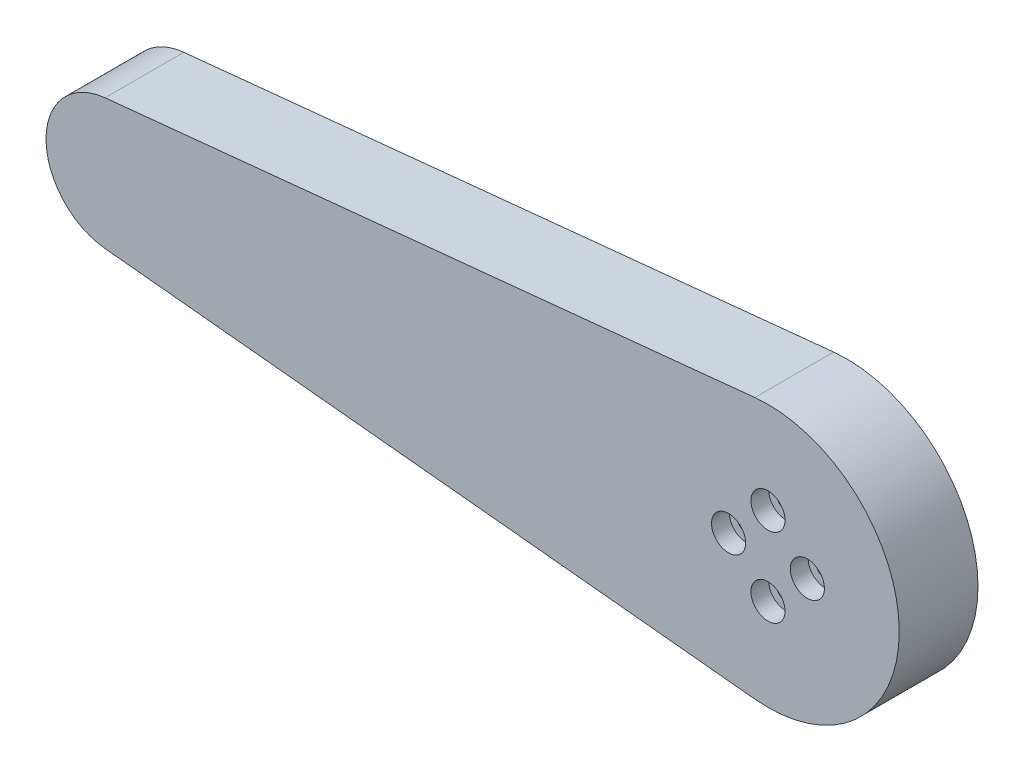
SolidWorks part; units mm, degrees
ref_plane "Front Plane" through (0, 0, 0) normal (0, 0, 1) x (1, 0, 0)
ref_plane "Top Plane" through (0, 0, 0) normal (0, 1, 0) x (1, 0, 0)
ref_plane "Right Plane" through (0, 0, 0) normal (1, 0, 0) x (0, 0, -1)
sketch "Sketch1" plane through (0, 0, 0) normal (0, 0, 1) x (1, 0, 0)
  line L0 (-126.25, 12.4373) -> (-2.5, 24.8747)
  line L1 (-126.25, -12.4373) -> (-2.5, -24.8747)
  circle A0 centre (0, 0) radius 12.5
  arc A1 (-2.5, -24.8747) -> (-2.5, 24.8747) centre (0, 0) ccw
  arc A2 (-126.25, 12.4373) -> (-126.25, -12.4373) centre (-125, 0) ccw
  dimension "D1" = 25
  dimension "D2" = 50
  dimension "D3" = 25
  dimension "D4" = 125
extrude "Boss-Extrude1" add sketch "Sketch1" along normal blind 15 contours L1 A1 L0 A2
hole_wizard "CBORE for M3 Hex Socket Head Cap Screw1" positions "Sketch3" profile "Sketch5" counterbore size "M3" standard "ISO" end condition up to next
sketch "Sketch3" plane through (0, 0, 15) normal (0, 0, 1) x (1, 0, 0)
  circle A0 centre (0, 0) radius 7.5
  point P0 (0, 7.5)
  point P13 (7.5, 0)
  point P15 (0, -7.5)
  point P17 (-7.5, 0)
  dimension "D1" = 15
sketch "Sketch5" plane through (0, 7.5, 15) normal (1, 0, 0) x (0, -1, 0)
  line L0 (0, 0) -> (0, 15)
  line L1 (0, 15) -> (1.7, 15)
  line L3 (1.7, 15) -> (1.7, 3.4)
  line L4 (1.7, 3.4) -> (3.25, 3.4)
  line L5 (3.25, 3.4) -> (3.25, 0)
  line L7 (3.25, 0) -> (0, 0)
  line L11 (0, -6.35) -> (0, 107.95) construction
  dimension "Thru Hole Dia." = 3.4
  dimension "Thru Hole Depth" = 15
  dimension "C'Bore Dia." = 6.5
  dimension "C'Bore Depth" = 3.4
sketch "Sketch2" [suppressed] plane through (0, 0, 15) normal (0, 0, 1) x (1, 0, 0)
  circle A0 centre (0, 0) radius 12.5 construction
  circle A1 centre (0, 0) radius 12.5
equation "\"roller_radius\"= 6.5"
equation "\"eccentricity\"= \"roller_radius\" * 0.325"
equation "\"outer_radius\"= 40"
equation "\"eccentric_shaft_radius\"= 16"
equation "\"rotor_width\"= 10"
equation "\"housing_depth\"= 40"
equation "\"bottom_depth\"= 5"
equation "\"roller_bearing_OD\"= \"roller_radius\" * 2"
equation "\"roller_bearing_ID\"= 6"
equation "\"eccentric_bearing_ID\"= 6"
equation "\"eccentric_bearing_OD\"= 15"
equation "\"roller_bearing_height\"= 5"
equation "\"eccentric_bearing_height\"= 5"
equation "\"bottom_bearing_ID\"= 15"
equation "\"bottom_bearing_OD\"= 32"
equation "\"bottom_bearing_height\"= 9"
equation "\"distance_to_output_rotor_holes\"= 20"
equation "\"output_bearing_ID\" = 25"
equation "\"output_bearing_OD\" = 37"
equation "\"output_bearing_height\" = 7"
equation "\"D1@Sketch1\"=\"output_bearing_ID\""
equation "\"D2@Sketch1\"=\"output_bearing_ID\"*2"
equation "\"D3@Sketch1\"=\"output_bearing_ID\""
equation "\"D4@Sketch1\"=\"D3@Sketch1\"*5"
